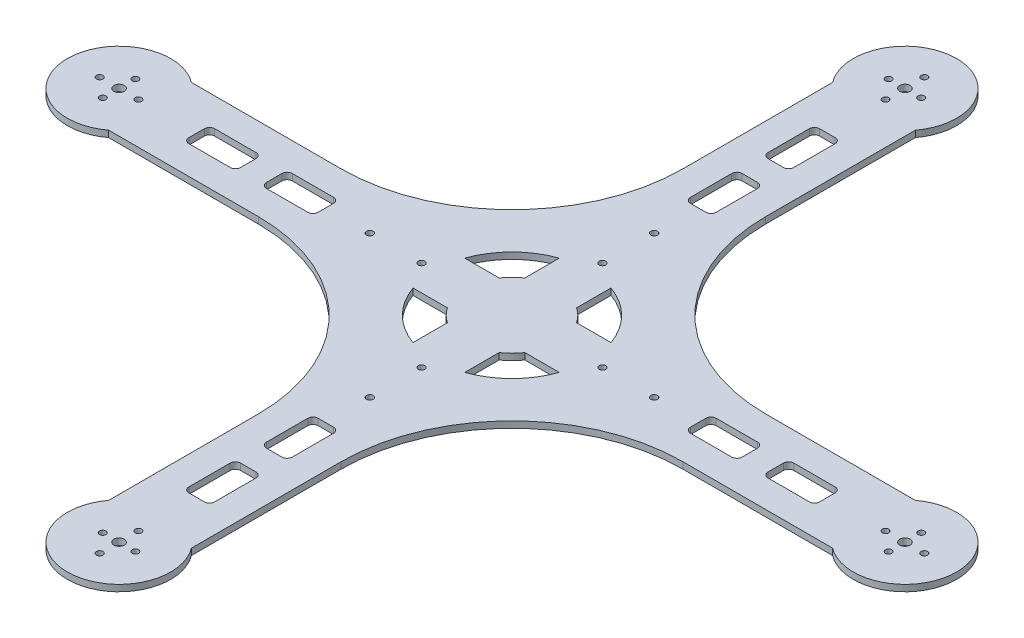
SolidWorks part; units mm, degrees
material "Acrylic (Medium-high impact)"
ref_plane "Front Plane" through (0, 0, 0) normal (0, 0, 1) x (1, 0, 0)
ref_plane "Top Plane" through (0, 0, 0) normal (0, 1, 0) x (1, 0, 0)
ref_plane "Right Plane" through (0, 0, 0) normal (1, 0, 0) x (0, 0, -1)
sketch "Sketch1" plane through (0, 0, 0) normal (0, 1, 0) x (1, 0, 0)
  line L0 (40.3016, -2.5359) -> (169.8416, -2.5359) construction
  line L1 (55.5416, 17.7841) -> (169.8416, 17.7841)
  line L2 (78.4016, -2.5359) -> (103.8016, -2.5359) construction
  line L3 (55.5416, -22.8559) -> (169.8416, -22.8559)
  line L4 (169.8416, 17.7841) -> (169.8416, -22.8559)
  line L5 (80.9416, 3.8141) -> (101.2616, 3.8141)
  line L6 (78.4016, 1.2741) -> (78.4016, -6.3459)
  line L7 (80.9416, -8.8859) -> (101.2616, -8.8859)
  line L8 (103.8016, 1.2741) -> (103.8016, -6.3459)
  line L9 (119.0416, 3.8141) -> (139.3616, 3.8141)
  line L10 (141.9016, 1.2741) -> (141.9016, -6.3459)
  line L11 (119.0416, -8.8859) -> (139.3616, -8.8859)
  line L12 (116.5016, 1.2741) -> (116.5016, -6.3459)
  line L21 (233.3416, 60.9641) -> (233.3416, -66.0359) construction
  line L22 (169.8416, -2.5359) -> (296.8416, -2.5359) construction
  line L23 (188.4403, -47.4372) -> (278.2428, 42.3654) construction
  line L24 (188.4403, 42.3654) -> (278.2428, -47.4372) construction
  line L25 (40.3016, 6.9641) -> (40.3016, -12.0359) construction
  line L26 (30.8016, -2.5359) -> (49.8016, -2.5359) construction
  line L27 (233.3416, -205.0759) -> (233.3416, -186.0759) construction
  line L28 (242.8416, -195.5759) -> (223.8416, -195.5759) construction
  line L29 (233.3416, -157.4759) -> (233.3416, -132.0759) construction
  line L30 (233.3416, -195.5759) -> (233.3416, -66.0359) construction
  line L39 (237.1516, -119.3759) -> (229.5316, -119.3759)
  line L40 (226.9916, -116.8359) -> (226.9916, -96.5159)
  line L41 (237.1516, -93.9759) -> (229.5316, -93.9759)
  line L42 (239.6916, -116.8359) -> (239.6916, -96.5159)
  line L43 (237.1516, -132.0759) -> (229.5316, -132.0759)
  line L44 (226.9916, -154.9359) -> (226.9916, -134.6159)
  line L45 (237.1516, -157.4759) -> (229.5316, -157.4759)
  line L46 (239.6916, -154.9359) -> (239.6916, -134.6159)
  line L47 (253.6616, -66.0359) -> (213.0216, -66.0359)
  line L48 (213.0216, -180.3359) -> (213.0216, -66.0359)
  line L49 (253.6616, -180.3359) -> (253.6616, -66.0359)
  line L50 (426.3816, -2.5359) -> (296.8416, -2.5359) construction
  line L51 (388.2816, -2.5359) -> (362.8816, -2.5359) construction
  line L52 (426.3816, -12.0359) -> (426.3816, 6.9641) construction
  line L53 (435.8816, -2.5359) -> (416.8816, -2.5359) construction
  line L54 (411.1416, -22.8559) -> (296.8416, -22.8559)
  line L55 (411.1416, 17.7841) -> (296.8416, 17.7841)
  line L56 (296.8416, -22.8559) -> (296.8416, 17.7841)
  line L57 (385.7416, -8.8859) -> (365.4216, -8.8859)
  line L58 (388.2816, -6.3459) -> (388.2816, 1.2741)
  line L59 (385.7416, 3.8141) -> (365.4216, 3.8141)
  line L60 (362.8816, -6.3459) -> (362.8816, 1.2741)
  line L61 (347.6416, -8.8859) -> (327.3216, -8.8859)
  line L62 (324.7816, -6.3459) -> (324.7816, 1.2741)
  line L63 (347.6416, 3.8141) -> (327.3216, 3.8141)
  line L64 (350.1816, -6.3459) -> (350.1816, 1.2741)
  line L73 (233.3416, 200.0041) -> (233.3416, 181.0041) construction
  line L74 (223.8416, 190.5041) -> (242.8416, 190.5041) construction
  line L75 (233.3416, 152.4041) -> (233.3416, 127.0041) construction
  line L76 (233.3416, 190.5041) -> (233.3416, 60.9641) construction
  line L85 (229.5316, 114.3041) -> (237.1516, 114.3041)
  line L86 (239.6916, 111.7641) -> (239.6916, 91.4441)
  line L87 (229.5316, 88.9041) -> (237.1516, 88.9041)
  line L88 (226.9916, 111.7641) -> (226.9916, 91.4441)
  line L89 (229.5316, 127.0041) -> (237.1516, 127.0041)
  line L90 (239.6916, 149.8641) -> (239.6916, 129.5441)
  line L91 (229.5316, 152.4041) -> (237.1516, 152.4041)
  line L92 (226.9916, 149.8641) -> (226.9916, 129.5441)
  line L93 (213.0216, 60.9641) -> (253.6616, 60.9641)
  line L94 (253.6616, 175.2641) -> (253.6616, 60.9641)
  line L95 (213.0216, 175.2641) -> (213.0216, 60.9641)
  line L96 (246.0416, -38.4569) -> (246.0416, -21.5435)
  line L97 (197.4205, 10.1641) -> (214.3339, 10.1641)
  line L99 (197.4205, -15.2359) -> (214.3339, -15.2359)
  line L100 (214.3339, 10.1641) -> (214.3339, -15.2359)
  line L101 (246.0416, -21.5435) -> (220.6416, -21.5435)
  line L102 (220.6416, -38.4569) -> (220.6416, -21.5435)
  line L105 (269.2626, -15.2359) -> (252.3492, -15.2359)
  line L106 (252.3492, -15.2359) -> (252.3492, 10.1641)
  line L107 (269.2626, 10.1641) -> (252.3492, 10.1641)
  line L108 (220.6416, 16.4717) -> (246.0416, 16.4717)
  line L109 (246.0416, 33.3852) -> (246.0416, 16.4717)
  line L111 (220.6416, 33.3852) -> (220.6416, 16.4717)
  circle A0 centre (40.3016, -2.5359) radius 25.4
  circle A1 centre (233.3416, -195.5759) radius 14 construction
  arc A2 (80.9416, -8.8859) -> (78.4016, -6.3459) centre (80.9416, -6.3459) cw
  arc A3 (103.8016, -6.3459) -> (101.2616, -8.8859) centre (101.2616, -6.3459) cw
  arc A4 (103.8016, 1.2741) -> (101.2616, 3.8141) centre (101.2616, 1.2741) ccw
  arc A5 (80.9416, 3.8141) -> (78.4016, 1.2741) centre (80.9416, 1.2741) ccw
  arc A6 (119.0416, 3.8141) -> (116.5016, 1.2741) centre (119.0416, 1.2741) ccw
  arc A7 (141.9016, 1.2741) -> (139.3616, 3.8141) centre (139.3616, 1.2741) ccw
  arc A8 (141.9016, -6.3459) -> (139.3616, -8.8859) centre (139.3616, -6.3459) cw
  arc A9 (119.0416, -8.8859) -> (116.5016, -6.3459) centre (119.0416, -6.3459) cw
  circle A10 centre (233.3416, -205.0759) radius 1.5875
  circle A11 centre (225.3416, -195.5759) radius 1.5875
  circle A12 centre (233.3416, -186.0759) radius 1.5875
  circle A13 centre (241.3416, -195.5759) radius 1.5875
  circle A14 centre (426.3816, 5.4641) radius 1.5875
  circle A15 centre (416.8816, -2.5359) radius 1.5875
  circle A16 centre (426.3816, -10.5359) radius 1.5875
  circle A17 centre (435.8816, -2.5359) radius 1.5875
  circle A18 centre (233.3416, -2.5359) radius 63.5
  circle A19 centre (40.3016, -2.5359) radius 8 construction
  circle A20 centre (40.3016, -2.5359) radius 9.5 construction
  circle A21 centre (40.3016, -2.5359) radius 14 construction
  circle A22 centre (233.3416, -195.5759) radius 9.5 construction
  circle A23 centre (233.3416, -195.5759) radius 8 construction
  circle A24 centre (233.3416, 200.0041) radius 1.5875
  circle A25 centre (241.3416, 190.5041) radius 1.5875
  circle A26 centre (233.3416, 181.0041) radius 1.5875
  circle A27 centre (225.3416, 190.5041) radius 1.5875
  circle A28 centre (40.3016, -2.5359) radius 2.54
  circle A29 centre (426.3816, -2.5359) radius 2.54
  circle A30 centre (233.3416, 190.5041) radius 2.54
  circle A31 centre (233.3416, -195.5759) radius 2.54
  arc A32 (226.9916, -116.8359) -> (229.5316, -119.3759) centre (229.5316, -116.8359) ccw
  arc A33 (229.5316, -93.9759) -> (226.9916, -96.5159) centre (229.5316, -96.5159) ccw
  arc A34 (237.1516, -93.9759) -> (239.6916, -96.5159) centre (237.1516, -96.5159) cw
  arc A35 (239.6916, -116.8359) -> (237.1516, -119.3759) centre (237.1516, -116.8359) cw
  arc A36 (239.6916, -154.9359) -> (237.1516, -157.4759) centre (237.1516, -154.9359) cw
  arc A37 (237.1516, -132.0759) -> (239.6916, -134.6159) centre (237.1516, -134.6159) cw
  arc A38 (229.5316, -132.0759) -> (226.9916, -134.6159) centre (229.5316, -134.6159) ccw
  arc A39 (226.9916, -154.9359) -> (229.5316, -157.4759) centre (229.5316, -154.9359) ccw
  circle A40 centre (233.3416, -195.5759) radius 25.4
  circle A41 centre (426.3816, -2.5359) radius 8 construction
  circle A42 centre (426.3816, -2.5359) radius 9.5 construction
  circle A43 centre (426.3816, -2.5359) radius 14 construction
  circle A44 centre (426.3816, -2.5359) radius 25.4
  arc A45 (385.7416, 3.8141) -> (388.2816, 1.2741) centre (385.7416, 1.2741) cw
  arc A46 (362.8816, 1.2741) -> (365.4216, 3.8141) centre (365.4216, 1.2741) cw
  arc A47 (362.8816, -6.3459) -> (365.4216, -8.8859) centre (365.4216, -6.3459) ccw
  arc A48 (385.7416, -8.8859) -> (388.2816, -6.3459) centre (385.7416, -6.3459) ccw
  arc A49 (347.6416, -8.8859) -> (350.1816, -6.3459) centre (347.6416, -6.3459) ccw
  arc A50 (324.7816, -6.3459) -> (327.3216, -8.8859) centre (327.3216, -6.3459) ccw
  arc A51 (324.7816, 1.2741) -> (327.3216, 3.8141) centre (327.3216, 1.2741) cw
  arc A52 (347.6416, 3.8141) -> (350.1816, 1.2741) centre (347.6416, 1.2741) cw
  circle A61 centre (233.3416, 190.5041) radius 14 construction
  circle A62 centre (233.3416, 190.5041) radius 9.5 construction
  circle A63 centre (233.3416, 190.5041) radius 8 construction
  arc A72 (239.6916, 111.7641) -> (237.1516, 114.3041) centre (237.1516, 111.7641) ccw
  arc A73 (237.1516, 88.9041) -> (239.6916, 91.4441) centre (237.1516, 91.4441) ccw
  arc A74 (229.5316, 88.9041) -> (226.9916, 91.4441) centre (229.5316, 91.4441) cw
  arc A75 (226.9916, 111.7641) -> (229.5316, 114.3041) centre (229.5316, 111.7641) cw
  arc A76 (226.9916, 149.8641) -> (229.5316, 152.4041) centre (229.5316, 149.8641) cw
  arc A77 (229.5316, 127.0041) -> (226.9916, 129.5441) centre (229.5316, 129.5441) cw
  arc A78 (237.1516, 127.0041) -> (239.6916, 129.5441) centre (237.1516, 129.5441) ccw
  arc A79 (239.6916, 149.8641) -> (237.1516, 152.4041) centre (237.1516, 149.8641) ccw
  circle A80 centre (233.3416, 190.5041) radius 25.4
  arc A81 (129.0958, 17.7841) -> (213.0216, 101.7099) centre (129.0958, 101.7099) ccw
  arc A82 (253.6616, -106.7816) -> (337.5873, -22.8559) centre (337.5873, -106.7816) cw
  arc A83 (253.6616, 101.7099) -> (337.5873, 17.7841) centre (337.5873, 101.7099) ccw
  arc A84 (129.0958, -22.8559) -> (213.0216, -106.7816) centre (129.0958, -106.7816) cw
  arc A85 (197.4205, -15.2359) -> (195.2416, -2.5359) centre (233.3416, -2.5359) ccw
  arc A87 (214.3339, -15.2359) -> (220.6416, -21.5435) centre (233.3416, -2.5359) ccw
  arc A88 (220.6416, 16.4717) -> (214.3339, 10.1641) centre (233.3416, -2.5359) ccw
  arc A89 (252.3492, 10.1641) -> (246.0416, 16.4717) centre (233.3416, -2.5359) ccw
  arc A90 (246.0416, -21.5435) -> (252.3492, -15.2359) centre (233.3416, -2.5359) ccw
  circle A91 centre (233.3416, -2.5359) radius 38.1
  circle A92 centre (40.3016, -10.5359) radius 1.5875
  circle A93 centre (40.3016, 5.4641) radius 1.5875
  circle A94 centre (30.8016, -2.5359) radius 1.5875
  circle A95 centre (49.8016, -2.5359) radius 1.5875
  point P19 (129.0958, 17.7841)
  point P23 (65.7016, -2.5359)
  point P75 (40.3016, 5.4641)
  point P76 (40.3016, -10.5359)
  point P78 (30.8016, -2.5359)
  point P79 (49.8016, -2.5359)
  point P142 (225.3416, -195.5759)
  point P143 (241.3416, -195.5759)
  point P144 (233.3416, -170.1759)
  point P145 (213.0216, 101.7099)
  point P210 (400.9816, -2.5359)
  point P211 (426.3816, -10.5359)
  point P212 (426.3816, 5.4641)
  point P276 (241.3416, 190.5041)
  point P277 (225.3416, 190.5041)
  point P278 (233.3416, 165.1041)
  dimension "D1" = 50.8
  dimension "D2" = 38.1
  dimension "D3" = 2.54
  dimension "D6" = 12.7
  dimension "D9" = 127
  dimension "D12" = 16
  dimension "D13" = 19
  dimension "D14" = 28
  dimension "D10" = 45.72
  dimension "D15" = 3.175
  dimension "D17" = 38.1
  dimension "D18" = 5.08
  dimension "D19" = 5.08
  dimension "D4" = 12.7
  dimension "D5" = 25.4
  dimension "D7" = 40.64
  dimension "D8" = 2
  dimension "D11" = 25.4
  dimension "D16" = 114.3
extrude "Boss-Extrude1" add sketch "Sketch1" along normal blind 3.175 contours L94 A80 L95 L93 L88 A75 L85 A72 L86 A73 L87 A74 A79 L90 A78 L89 A77 L92 A76 L91 | A18 A91 A85 | A81 A18 L93 L95 | A81 L1 L4 A18 | A0 L3 L4 L1 A5 L5 A4 L8 A3 L7 A2 L6 L11 A9 L12 A6 L9 A7 L10 A8 | A0 A95 A94 A93 A92 | L3 A84 A18 L4 | A18 A84 L48 L47 | L48 A40 L49 L47 L42 A35 L39 A32 L40 A33 L41 A34 A39 L44 A38 L43 A37 L46 A36 L45 | A40 A13 A11 A10 A12 | L49 A82 A18 L47 | A18 A82 L54 L56 | A44 L55 L56 L54 A48 L57 A47 L60 A46 L59 A45 L58 L63 A52 L64 A49 L61 A50 L62 A51 | A83 A18 L56 L55 | A83 L94 L93 A18 | A44 A17 A16 A15 A14 | A80 A27 A25 A24 A26 | L101 A90 L106 A89 L108 A88 L100 A87 | L102 A85 L96 L101 | L105 A85 L107 L106 | A85 A91 L99 L100 L97 | L109 A85 L111 L108 region at (92.3187, 0, -16.571) region at (62.3774, 0, -8.5021) region at (166.22, 0, -22.4002) region at (208.4055, 0, -64.5857) region at (209.7285, 0, -54.4711) region at (166.22, 0, 27.472) region at (223.1816, 0, -62.1772) region at (258.2777, 0, -64.5857) region at (208.4055, 0, 69.6574) region at (300.4631, 0, -22.4002) region at (225.5366, 0, -213.9191) region at (258.2777, 0, 69.6574) region at (243.5016, 0, 67.249) region at (298.0547, 0, -7.6241) region at (300.4631, 0, 27.472) region at (233.3416, 0, 170.8943) region at (437.4195, 0, -19.54) region at (233.3416, 0, 30.7422) region at (233.3416, 0, 2.5359) region at (261.5479, 0, 2.5359) region at (205.1353, 0, 2.5359) region at (233.3416, 0, -25.6704)
ref_plane "Plane1" through (233.3416, 0, 0) normal (1, 0, 0) x (0, 0, -1)
ref_plane "Plane2" through (0, 0, 2.5359) normal (0, 0, 1) x (1, 0, 0)
sketch "Sketch5" plane through (0, 0, 0) normal (0, -1, 0) x (1, 0, 0)
  line L0 (220.6416, 46.9859) -> (246.0416, 46.9859) construction
  line L1 (233.3416, -6.6955) -> (233.3416, 6.6955) construction
  line L2 (277.7916, 15.2359) -> (277.7916, -10.1641) construction
  line L3 (303.1916, 15.2359) -> (303.1916, -10.1641) construction
  line L4 (246.0416, -41.9141) -> (220.6416, -41.9141) construction
  line L5 (246.0416, -67.3141) -> (220.6416, -67.3141) construction
  line L6 (163.4916, -10.1641) -> (163.4916, 15.2359) construction
  line L7 (188.8916, -10.1641) -> (188.8916, 15.2359) construction
  circle A0 centre (233.3416, 46.9859) radius 1.651
  circle A1 centre (233.3416, 72.3859) radius 1.651
  circle A2 centre (277.7916, 2.5359) radius 1.651
  circle A3 centre (303.1916, 2.5359) radius 1.651
  circle A4 centre (233.3416, -41.9141) radius 1.651
  circle A5 centre (233.3416, -67.3141) radius 1.651
  circle A6 centre (163.4916, 2.5359) radius 1.651
  circle A7 centre (188.8916, 2.5359) radius 1.651
extrude "Cut-Extrude1" cut sketch "Sketch5" against normal up to next
equation "\"ARM_TOTAL_LENGTH\"= 4.5"
equation "\"ARM_TOTAL_WIDTH\"= 1.6in"
equation "\"MOTOR_MOUNT_TOTAL_RADIUS\"= 1in"
equation "\"MOTOR_CAVITY_RADIUS\"= 1in"
equation "\"D1@Sketch1\"=\"MOTOR_MOUNT_TOTAL_RADIUS\" * 2"
equation "\"D7@Sketch1\"=\"ARM_TOTAL_WIDTH\""
equation "\"BODY_DIAMETER\"= 3in"
equation "\"MOTOR_DIAMETER\"= 28mm"
equation "\"D14@Sketch1\"=\"MOTOR_DIAMETER\""
equation "\"D16@Sketch1\"=\"ARM_TOTAL_LENGTH\""
equation "\"D2@Sketch1\"=\"BODY_DIAMETER\"/2"
